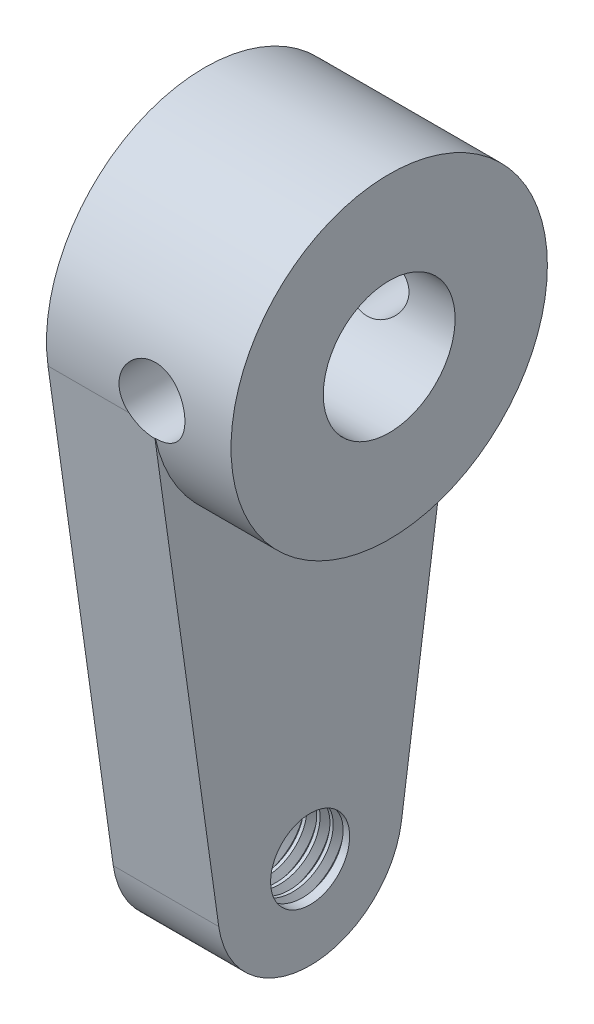
SolidWorks part; units mm, degrees
ref_plane "Front Plane" through (0, 0, 0) normal (0, 0, 1) x (1, 0, 0)
ref_plane "Top Plane" through (0, 0, 0) normal (0, 1, 0) x (1, 0, 0)
ref_plane "Right Plane" through (0, 0, 0) normal (1, 0, 0) x (0, 0, -1)
sketch "Sketch1" plane through (0, 0, 0) normal (1, 0, 0) x (0, 0, -1)
  line L0 (5.9418, -0.8333) -> (3.4661, -18.4861)
  line L1 (-5.9418, -0.8333) -> (-3.4661, -18.4861)
  arc A0 (5.9418, -0.8333) -> (-5.9418, -0.8333) centre (0, 0) ccw
  arc A1 (-3.4661, -18.4861) -> (3.4661, -18.4861) centre (0, -18) ccw
  point P9 (0, 0)
  dimension "D1" = 12
  dimension "D2" = 18
  dimension "D3" = 7
extrude "Boss-Extrude1" add sketch "Sketch1" along normal blind 4
sketch "Sketch2" plane through (4, 0, 0) normal (1, 0, 0) x (0, 0, -1)
  circle A0 centre (0, 0) radius 6
  dimension "D1" = 12
extrude "Boss-Extrude2" add sketch "Sketch2" along normal blind 3
sketch "Sketch3" plane through (0, 0, 0) normal (-1, 0, 0) x (0, 0, 1)
  circle A0 centre (0, 0) radius 2.5
  circle A1 centre (0, -18) radius 1.5
  dimension "D1" = 5
  dimension "D2" = 3
extrude "Cut-Extrude1" cut sketch "Sketch3" against normal through all both and the other way through all
thread "Thread1" pitch 0.5 method cut profile "Thread Profile1" start angle 0, offset 0, length 8, pitch 0.5, diameter 3
ref_plane "Plane1" through (4, -18, 1.5) normal (0, -1, 0) x (0, 0, 1)
sketch "Thread Profile1" plane through (4, -18, 1.5) normal (0, -1, 0) x (0, 0, 1)
  line L0 (0, 0) -> (0, 0.5) construction
  line L1 (0, 0) -> (0.2706, 0.1562)
  line L2 (0.2706, 0.1562) -> (0.2706, 0.2187)
  line L3 (0.2706, 0.2187) -> (0, 0.375)
  line L4 (0.2706, 0.1875) -> (0, 0.1875) construction
  line L11 (0, 0) -> (0, 0.375)
  point P2 (0, 0)
  dimension "Pitch" = 0.5
  dimension "Profile_Angle" = 60
  dimension "Profile_Land" = 0.0625
  dimension "Profile_Height" = 0.2706
sketch "Sketch6" plane through (0, 0, 0) normal (0, 0, 1) x (1, 0, 0)
  line L1 (7, -6) -> (7, 6) construction
  circle A1 centre (4, 0) radius 1.25
  dimension "D1" = 2.5
  dimension "D2" = 3
extrude "Cut-Extrude2" cut sketch "Sketch6" against normal through all both and the other way through all
